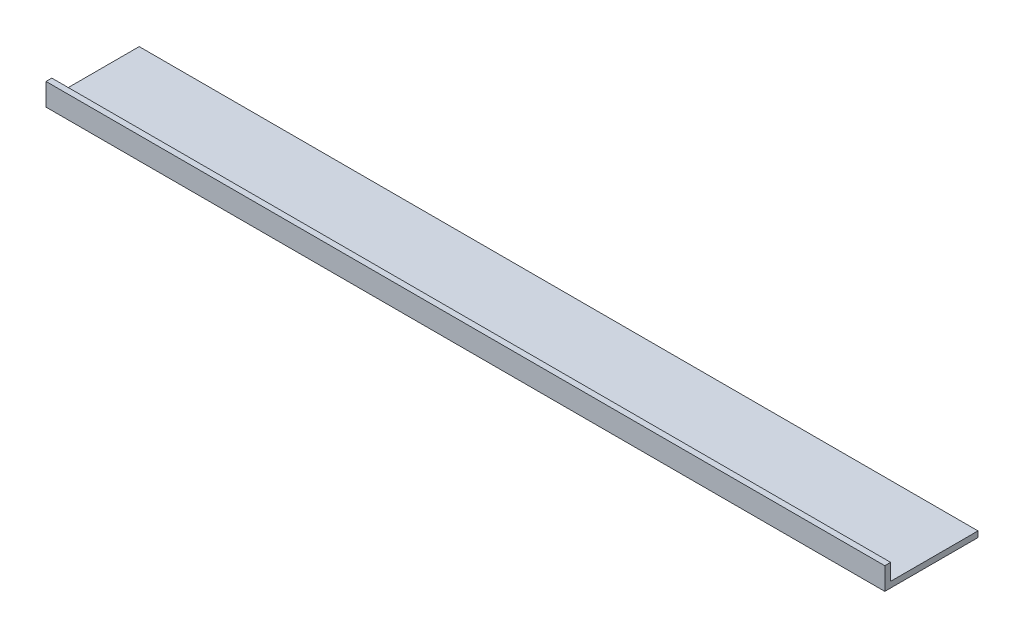
SolidWorks part; units mm, degrees
ref_plane "Front Plane" through (0, 0, 0) normal (0, 0, 1) x (1, 0, 0)
ref_plane "Top Plane" through (0, 0, 0) normal (0, 1, 0) x (1, 0, 0)
ref_plane "Right Plane" through (0, 0, 0) normal (1, 0, 0) x (0, 0, -1)
sketch "Sketch1" plane through (0, 0, 0) normal (1, 0, 0) x (0, 0, -1)
  line L1 (0, 0) -> (50.8, 0)
  line L2 (0, 0) -> (0, 12.1323)
  line L3 (0, 12.1323) -> (50.8, 12.1323)
  line L4 (50.8, 0) -> (50.8, 12.1323)
  dimension "D1" = 12.1323
  dimension "D2" = 50.8
extrude "Boss-Extrude1" add sketch "Sketch1" along normal blind 457.2 contours L2 L1 L4 L3
sketch "Sketch2" plane through (0, 0, 0) normal (-1, 0, 0) x (0, 0, 1)
  line L0 (-41.275, 12.1323) -> (-3.175, 12.1323)
  line L2 (-41.275, 3.175) -> (-3.175, 3.175)
  line L3 (-3.175, 12.1323) -> (-3.175, 3.175)
  line L4 (0, 12.1323) -> (-50.8, 12.1323) construction
  line L5 (-41.275, 3.175) -> (-50.8, 3.175)
  line L6 (-50.8, 0) -> (-50.8, 12.1323) construction
  line L7 (-50.8, 3.175) -> (-50.8, 12.1323)
  line L8 (-41.275, 12.1323) -> (-50.8, 12.1323)
extrude "Cut-Extrude1" cut sketch "Sketch2" against normal blind 457.2
